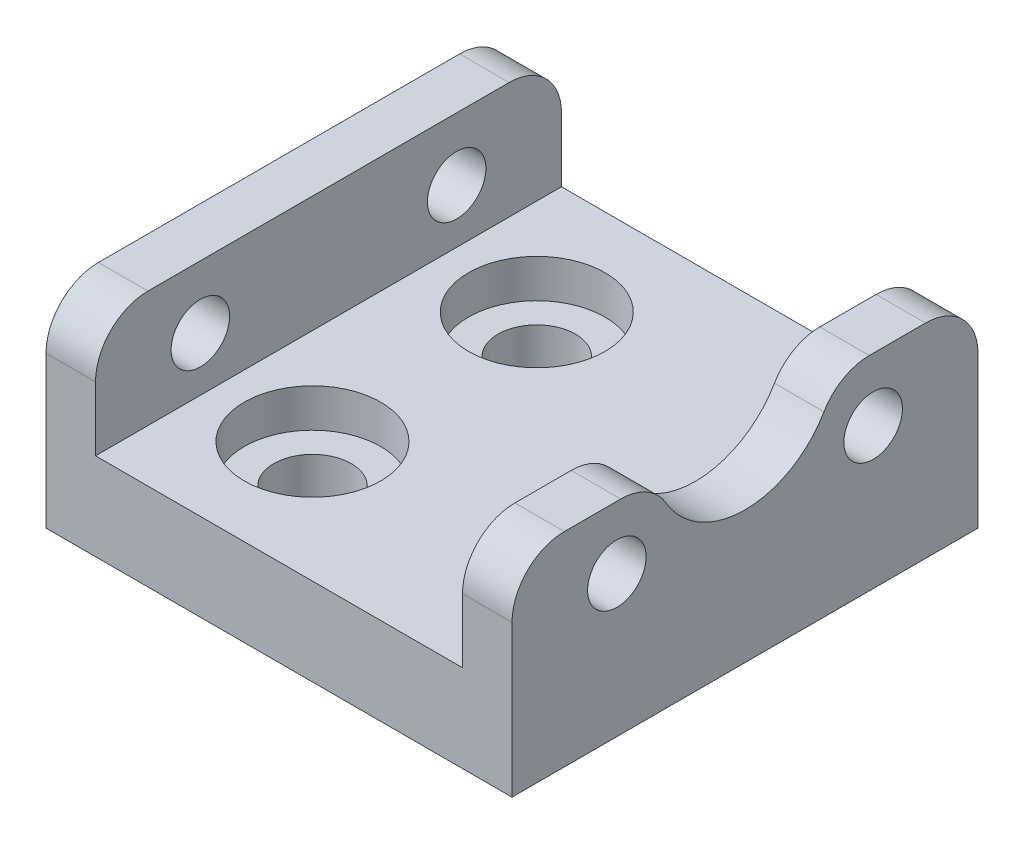
SolidWorks part; units mm, degrees
material "ABS"
ref_plane "Front" through (0, 0, 0) normal (0, 0, 1) x (1, 0, 0)
ref_plane "Top" through (0, 0, 0) normal (0, 1, 0) x (1, 0, 0)
ref_plane "Right" through (0, 0, 0) normal (1, 0, 0) x (0, 0, -1)
ref_axis "Axis1" through (0, 0, 55) along (0, 0, -1)
sketch "Sketch1" plane through (0, 0, 0) normal (0, 1, 0) x (1, 0, 0)
  line L1 (0, 0) -> (40.64, 0)
  line L2 (0, 0) -> (0, -40.64)
  line L3 (0, -40.64) -> (40.64, -40.64)
  line L4 (40.64, 0) -> (40.64, -40.64)
  line L5 (0, 0) -> (40.64, -40.64) construction
  line L6 (0, -40.64) -> (40.64, 0) construction
  point P4 (20.32, -20.32)
  dimension "D1" = 40.64
  dimension "D2" = 40.64
extrude "Boss-Extrude1" add sketch "Sketch1" along normal blind 7.62
sketch "Sketch2" plane through (0, 7.62, 0) normal (0, 1, 0) x (1, 0, 0)
  line L0 (0, -40.64) -> (40.64, -40.64) construction
  line L1 (0, 0) -> (4.318, 0)
  line L2 (0, 0) -> (0, -40.64)
  line L3 (0, -40.64) -> (4.318, -40.64)
  line L4 (4.318, 0) -> (4.318, -40.64)
  line L5 (0, 0) -> (4.318, -40.64) construction
  line L6 (0, -40.64) -> (4.318, 0) construction
  line L7 (40.64, 0) -> (0, 0) construction
  line L8 (36.322, 0) -> (40.64, 0)
  line L9 (36.322, 0) -> (36.322, -40.64)
  line L10 (36.322, -40.64) -> (40.64, -40.64)
  line L11 (40.64, 0) -> (40.64, -40.64)
  line L12 (36.322, 0) -> (40.64, -40.64) construction
  line L13 (36.322, -40.64) -> (40.64, 0) construction
  point P4 (2.159, -20.32)
  point P12 (38.481, -20.32)
  dimension "D1" = 32.004
extrude "Boss-Extrude2" add sketch "Sketch2" along normal blind 10.16
hole_wizard "#10 Clearance Hole1" positions "Sketch4" profile "Sketch5" hole size "#10" standard "ANSI Inch" end condition through all
sketch "Sketch4" plane through (0, 0, 0) normal (-1, 0, 0) x (0, 0, 1)
  line L0 (0, 12.319) -> (40.64, 12.319) construction
  line L1 (0, 17.78) -> (0, 0) construction
  line L2 (40.64, 17.78) -> (40.64, 0) construction
  point P0 (9.144, 12.319)
  point P2 (31.496, 12.319)
  dimension "D1" = 31.496
sketch "Sketch5" plane through (0, 12.319, 9.144) normal (0, 1, 0) x (0, 0, 1)
  line L0 (0, 0) -> (0, 40.64)
  line L1 (0, 40.64) -> (2.5527, 40.64)
  line L2 (2.5527, 40.64) -> (2.5527, 0)
  line L5 (2.5527, 0) -> (0, 0)
  line L11 (0, -6.35) -> (0, 107.95) construction
  dimension "Thru Hole Dia." = 5.1054
  dimension "Thru Hole Depth" = 40.64
hole_wizard "CBORE for 1/4 Button Head Cap Screw1" positions "Sketch6" profile "Sketch7" counterbore size "1/4" standard "ANSI Inch" end condition through all
sketch "Sketch6" plane through (0, 7.62, 0) normal (0, 1, 0) x (1, 0, 0)
  line L0 (36.322, -20.32) -> (4.318, -20.32) construction
  line L1 (36.322, 0) -> (36.322, -40.64) construction
  line L2 (4.318, -40.64) -> (4.318, 0) construction
  line L4 (12.7, -10.541) -> (12.7, -30.099) construction
  point P0 (12.7, -10.541)
  point P2 (12.7, -30.099)
  dimension "D1" = 8.382
  dimension "D2" = 19.558
sketch "Sketch7" plane through (12.7, 7.62, 10.541) normal (1, 0, 0) x (0, 0, 1)
  line L0 (0, 0) -> (0, 7.62)
  line L1 (0, 7.62) -> (3.3782, 7.62)
  line L3 (3.3782, 7.62) -> (3.3782, 3.3528)
  line L4 (3.3782, 3.3528) -> (5.9538, 3.3528)
  line L5 (5.9538, 3.3528) -> (5.9538, 0)
  line L7 (5.9538, 0) -> (0, 0)
  line L11 (0, -6.35) -> (0, 107.95) construction
  dimension "Thru Hole Dia." = 6.7564
  dimension "Thru Hole Depth" = 7.62
  dimension "C'Bore Dia." = 11.9075
  dimension "C'Bore Depth" = 3.3528
sketch "Sketch8" plane through (40.64, 0, 0) normal (1, 0, 0) x (0, 0, -1)
  line L0 (-20.32, 0) -> (-20.32, 19.5046) construction
  line L1 (-40.64, 0) -> (0, 0) construction
  circle A0 centre (-20.32, 19.5046) radius 7.9654
  dimension "D1" = 15.9307
  dimension "D2" = 19.5046
extrude "Cut-Extrude1" cut sketch "Sketch8" against normal up to next
fillet "Fillet1" radius 4.572 6 edges at (38.481, 17.78, 28.0964) (38.481, 17.78, 12.5436) (38.481, 17.78, 0) (38.481, 17.78, 40.64) (2.159, 17.78, 0) (2.159, 17.78, 40.64)
